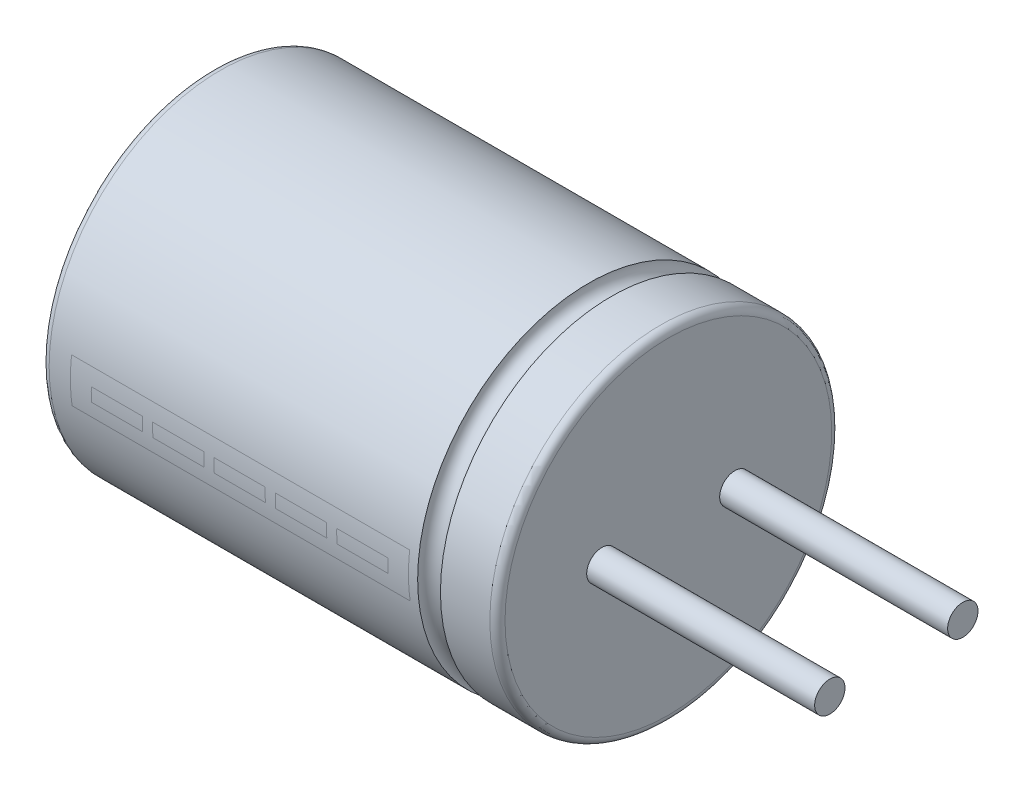
SolidWorks part; units mm, degrees
ref_plane "Front Plane" through (0, 0, 0) normal (0, 0, 1) x (1, 0, 0)
ref_plane "Top Plane" through (0, 0, 0) normal (0, 1, 0) x (1, 0, 0)
ref_plane "Right Plane" through (0, 0, 0) normal (1, 0, 0) x (0, 0, -1)
sketch "Sketch1" plane through (0, 0, 0) normal (0, 1, 0) x (1, 0, 0)
  line L0 (-5.95, -1.25) -> (-6.05, -1.25)
  line L1 (-5.95, 2.25) -> (5.95, 2.25)
  line L2 (-5.95, 2.25) -> (-5.95, -1.25)
  line L3 (-5.95, -2.25) -> (3.85, -2.25)
  line L4 (5.95, 2.25) -> (5.95, -2.25)
  line L5 (4.45, -2.25) -> (5.95, -2.25)
  line L6 (-6.05, -2.25) -> (-5.95, -2.25)
  line L7 (-6.05, -1.25) -> (-6.05, -2.25)
  arc A0 (3.85, -2.25) -> (4.45, -2.25) centre (4.15, -2.25) cw
  point P0 (0, 0)
  dimension "D3" = 0.3
  dimension "D1" = 11.9
  dimension "D2" = 4.5
  dimension "D4" = 1.5
  dimension "D5" = 0.1
  dimension "D6" = 1
revolve "Revolve1" add sketch "Sketch1" angle 360 about L1
sketch "Sketch6" plane through (5.95, 0, 0) normal (1, 0, 0) x (0, 0, -1)
  line L0 (-2.25, 0) -> (0, 0) construction
  line L1 (0, 0) -> (6.75, 0) construction
  line L2 (6.75, 0) -> (2.25, 4.5) construction
  line L3 (2.25, 4.5) -> (2.25, -4.5) construction
  circle A0 centre (2.25, 0) radius 4.5 construction
  circle A1 centre (0.5, 0) radius 0.4
  circle A2 centre (4, 0) radius 0.4
  dimension "D1" = 0.8
  dimension "D2" = 1.75
  dimension "D3" = 2
extrude "Boss-Extrude1" add sketch "Sketch6" along normal blind 6
sketch "Sketch8" plane through (-5.95, 0, 0) normal (-1, 0, 0) x (0, 0, 1)
  line L2 (-2.25, 3.5) -> (-2.25, 3.325) construction
  line L3 (-2, -0.25) -> (-2, -3.325)
  line L4 (-2.5, 3.325) -> (-2, 3.325)
  line L5 (-2.5, 3.325) -> (-2.5, 0.25)
  line L6 (-2.5, -3.325) -> (-2, -3.325)
  line L7 (-2, 3.325) -> (-2, 0.25)
  line L10 (-5.575, 0.25) -> (-2.5, 0.25)
  line L11 (-5.575, 0.25) -> (-5.575, -0.25)
  line L12 (-5.575, -0.25) -> (-2.5, -0.25)
  line L13 (1.075, 0.25) -> (1.075, -0.25)
  line L17 (-2.25, -3.325) -> (-2.25, -3.5) construction
  line L19 (-2.5, -0.25) -> (-2.5, -3.325)
  line L24 (-2, -0.25) -> (1.075, -0.25)
  line L25 (-2, 0.25) -> (1.075, 0.25)
  circle A0 centre (-2.25, 0) radius 3.5 construction
  circle A1 centre (-2.25, 0) radius 3.5 construction
  point P9 (-2.25, 0)
  point P14 (-2.25, 0)
  dimension "D1" = 0.5
  dimension "D2" = 6.65
  dimension "D3" = 6.65
  dimension "D4" = 0.5
extrude "Cut-Extrude1" cut sketch "Sketch8" against normal blind 0.2
fillet "Fillet2" radius 0.2 26 edges at (-5.75, -3.325, -2.25) (-5.85, -3.325, -2) (-5.75, -1.7875, -2.5) (-5.85, -3.325, -2.5) (-5.75, -0.25, -4.0375) (-5.85, -0.25, -2.5) (-5.75, 0, -5.575) (-5.85, -0.25, -5.575) (-5.75, 0.25, -4.0375) (-5.85, 0.25, -5.575) (-5.75, 1.7875, -2.5) (-5.85, 0.25, -2.5) (-5.75, 3.325, -2.25) (-5.85, 3.325, -2.5) (-5.75, 1.7875, -2) (-5.85, 3.325, -2) (-5.75, 0.25, -0.4625) (-5.85, 0.25, -2) (-5.75, 0, 1.075) (-5.85, 0.25, 1.075) (-5.75, -0.25, -0.4625) (-5.85, -0.25, 1.075) (-5.75, -1.7875, -2) (-5.85, -0.25, -2) (5.95, 0, 2.25) (-6.05, 0, 2.25)
ref_plane "Plane1" through (0, 0, 10) normal (0, 0, 1) x (1, 0, 0)
sketch "Sketch9" plane through (0, 0, 10) normal (0, 0, 1) x (1, 0, 0)
  line L1 (3.608, 0.5314) -> (-5.2906, 0.5314)
  line L2 (3.608, 0.5314) -> (3.608, -0.6395)
  line L3 (3.608, -0.6395) -> (-5.2906, -0.6395)
  line L4 (-5.2906, 0.5314) -> (-5.2906, -0.6395)
  text T0 "-----"
  dimension "D1" = 1.1709
split line "Split Line1"
